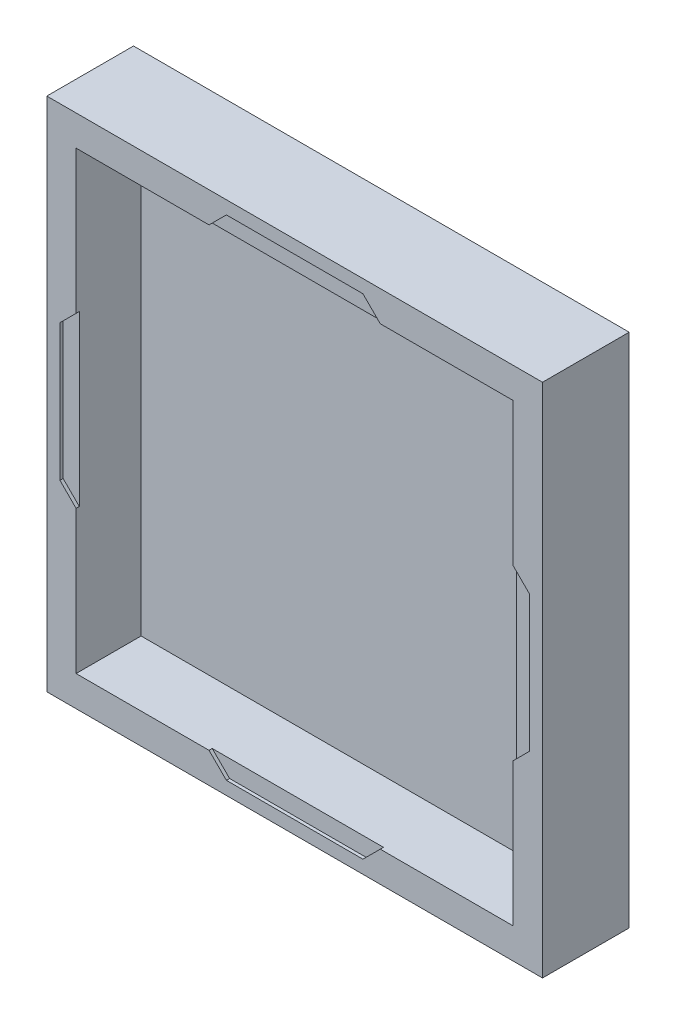
SolidWorks part; units mm, degrees
ref_plane "Front Plane" through (0, 0, 0) normal (1, 0, 0) x (0, 1, 0)
ref_plane "Top Plane" through (0, 0, 0) normal (0, 0, 1) x (0, 1, 0)
ref_plane "Right Plane" through (0, 0, 0) normal (0, 1, 0) x (-1, 0, 0)
sketch "Sketch1" plane through (0, 0, 0) normal (0, 0, 1) x (0, 1, 0)
  line L1 (-55.3847, -53.0098) -> (55.3847, -53.0098) construction
  line L2 (-55.3847, -53.0098) -> (-55.3847, 53.0098) construction
  line L3 (-55.3847, 53.0098) -> (55.3847, 53.0098) construction
  line L4 (55.3847, -53.0098) -> (55.3847, 53.0098) construction
  line L5 (-55.3847, -53.0098) -> (55.3847, 53.0098) construction
  line L6 (-55.3847, 53.0098) -> (55.3847, -53.0098) construction
  line L7 (-60.4647, -58.0898) -> (60.4647, -58.0898)
  line L8 (-60.4647, -58.0898) -> (-60.4647, 58.0898)
  line L9 (-60.4647, 58.0898) -> (60.4647, 58.0898)
  line L10 (60.4647, -58.0898) -> (60.4647, 58.0898)
  line L11 (-60.4647, -58.0898) -> (60.4647, 58.0898) construction
  line L12 (-60.4647, 58.0898) -> (60.4647, -58.0898) construction
  line L13 (-52.3875, -50.0126) -> (52.3875, -50.0126) construction
  line L14 (-52.3875, -50.0126) -> (-52.3875, 50.0126) construction
  line L15 (-52.3875, 50.0126) -> (52.3875, 50.0126) construction
  line L16 (52.3875, -50.0126) -> (52.3875, 50.0126) construction
  line L17 (-52.3875, -50.0126) -> (52.3875, 50.0126) construction
  line L18 (-52.3875, 50.0126) -> (52.3875, -50.0126) construction
  point P0 (0, 0)
  point P6 (0, 0)
  point P11 (0, 0)
  dimension "D1" = 106.0196
  dimension "D2" = 110.7694
  dimension "D3" = 5.08
  dimension "D4" = 5.08
  dimension "D5" = 104.775
  dimension "D6" = 100.0252
extrude "Boss-Extrude1" add sketch "Sketch1" along normal blind 5.08
sketch "Sketch2" plane through (0, 0, 5.08) normal (0, 0, 1) x (1, 0, 0)
  line L1 (58.0898, -60.4647) -> (-58.0898, -60.4647)
  line L2 (58.0898, -60.4647) -> (58.0898, 60.4647)
  line L3 (58.0898, 60.4647) -> (-58.0898, 60.4647)
  line L4 (-58.0898, -60.4647) -> (-58.0898, 60.4647)
  line L5 (58.0898, -60.4647) -> (-58.0898, 60.4647) construction
  line L6 (58.0898, 60.4647) -> (-58.0898, -60.4647) construction
  line L7 (50.2688, -52.324) -> (-50.2688, -52.324) construction
  line L8 (50.2688, -52.324) -> (50.2688, 52.324) construction
  line L9 (50.2688, 52.324) -> (-50.2688, 52.324) construction
  line L10 (-50.2688, -52.324) -> (-50.2688, 52.324) construction
  line L11 (50.2688, -52.324) -> (-50.2688, 52.324) construction
  line L12 (50.2688, 52.324) -> (-50.2688, -52.324) construction
  line L13 (-51.2296, -53.324) -> (51.2296, -53.324)
  line L14 (-51.2296, -53.324) -> (-51.2296, 53.324)
  line L15 (-51.2296, 53.324) -> (51.2296, 53.324)
  line L16 (51.2296, -53.324) -> (51.2296, 53.324)
  line L17 (-51.2296, -53.324) -> (51.2296, 53.324) construction
  line L18 (-51.2296, 53.324) -> (51.2296, -53.324) construction
  point P0 (0, 0)
  point P7 (0, 0)
  point P12 (0, 0)
  dimension "D1" = 104.648
  dimension "D2" = 1
extrude "Boss-Extrude2" add sketch "Sketch2" along normal blind 15.24
sketch "Sketch3" plane through (0, 0, 20.32) normal (0, 0, 1) x (1, 0, 0)
  line L0 (-50.0126, 0) -> (50.0126, 0) construction
  line L1 (-50.0126, -52.3875) -> (-21, -52.3875)
  line L2 (-50.0126, -52.3875) -> (-50.0126, -21)
  line L3 (-50.0126, 52.3875) -> (-21, 52.3875)
  line L4 (50.0126, -52.3875) -> (50.0126, -21)
  line L5 (-50.0126, -52.3875) -> (50.0126, 52.3875) construction
  line L6 (-50.0126, 52.3875) -> (50.0126, -52.3875) construction
  line L7 (0, 52.3875) -> (0, -52.3875) construction
  line L8 (50.0126, 0) -> (55.0126, 0) construction
  line L9 (55.0126, -16) -> (55.0126, 16)
  line L10 (50.0126, 21) -> (50.0126, 52.3875)
  line L11 (50.0126, -21) -> (50.0126, 21) construction
  line L12 (55.0126, 16) -> (50.0126, 21)
  line L13 (55.0126, -16) -> (50.0126, -21)
  line L14 (-21, -52.3875) -> (21, -52.3875) construction
  line L15 (21, -52.3875) -> (50.0126, -52.3875)
  line L16 (-50.0126, -21) -> (-50.0126, 21) construction
  line L17 (-50.0126, 21) -> (-50.0126, 52.3875)
  line L18 (-21, 52.3875) -> (21, 52.3875) construction
  line L19 (21, 52.3875) -> (50.0126, 52.3875)
  line L20 (0, 52.3875) -> (0, 57.3875) construction
  line L21 (-50.0126, 0) -> (-55.0126, 0) construction
  line L22 (0, -52.3875) -> (0, -57.3875) construction
  line L23 (-16, -57.3875) -> (16, -57.3875)
  line L24 (-55.0126, 16) -> (-55.0126, -16)
  line L25 (-16, 57.3875) -> (16, 57.3875)
  line L26 (16, 57.3875) -> (21, 52.3875)
  line L27 (-21, 52.3875) -> (-16, 57.3875)
  line L28 (-55.0126, 16) -> (-50.0126, 21)
  line L29 (-50.0126, -21) -> (-55.0126, -16)
  line L30 (-16, -57.3875) -> (-21, -52.3875)
  line L31 (16, -57.3875) -> (21, -52.3875)
  point P0 (0, 0)
  point P13 (55.0126, 0)
  point P31 (0, -57.3875)
  point P32 (-55.0126, 0)
  point P33 (0, 57.3875)
  dimension "D1" = 104.775
  dimension "D2" = 100.0252
  dimension "D3" = 5
  dimension "D4" = 32
  dimension "D5" = 135
  dimension "D6" = 135
  dimension "D7" = 135
  dimension "D8" = 135
extrude "Cut-Extrude1" cut sketch "Sketch3" against normal blind 0.75
